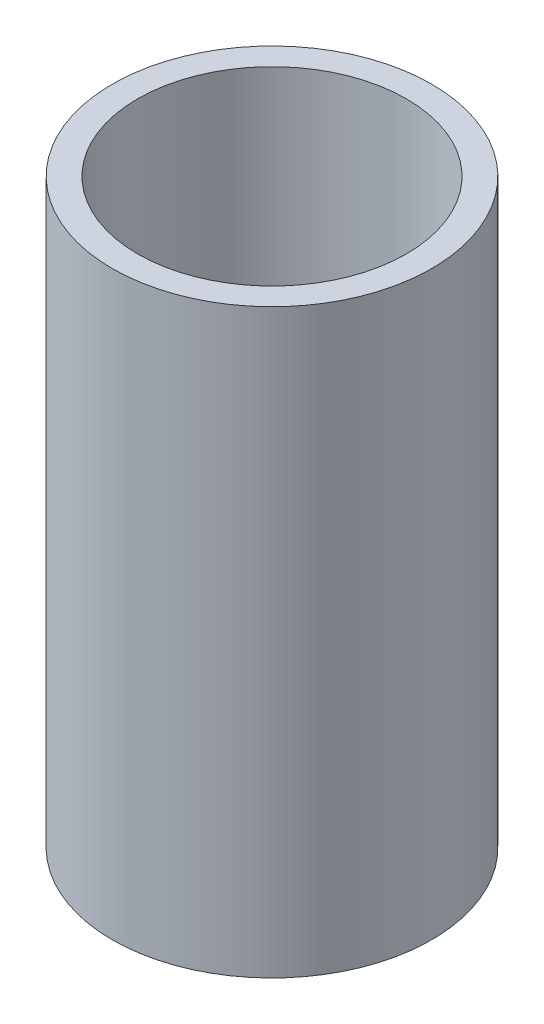
SolidWorks part; units mm, degrees
ref_plane "Front Plane" through (0, 0, 0) normal (0, 0, 1) x (1, 0, 0)
ref_plane "Top Plane" through (0, 0, 0) normal (0, 1, 0) x (1, 0, 0)
ref_plane "Right Plane" through (0, 0, 0) normal (1, 0, 0) x (0, 0, -1)
sketch "Sketch1" plane through (0, 0, 0) normal (0, 1, 0) x (1, 0, 0)
  circle A0 centre (0, 0) radius 30
  dimension "SLEEVE_OD" = 60
extrude "Boss-Extrude1" add sketch "Sketch1" along normal blind 109.2055
sketch "Sketch2" plane through (0, 0, 0) normal (0, 1, 0) x (1, 0, 0)
  circle A0 centre (0, 0) radius 25.2428
  dimension "BORE_D" = 50.4855
extrude "Cut-Extrude1" cut sketch "Sketch2" along normal through all
chamfer "Chamfer1" distance 2.8684 angle 60 rebuild error yes
